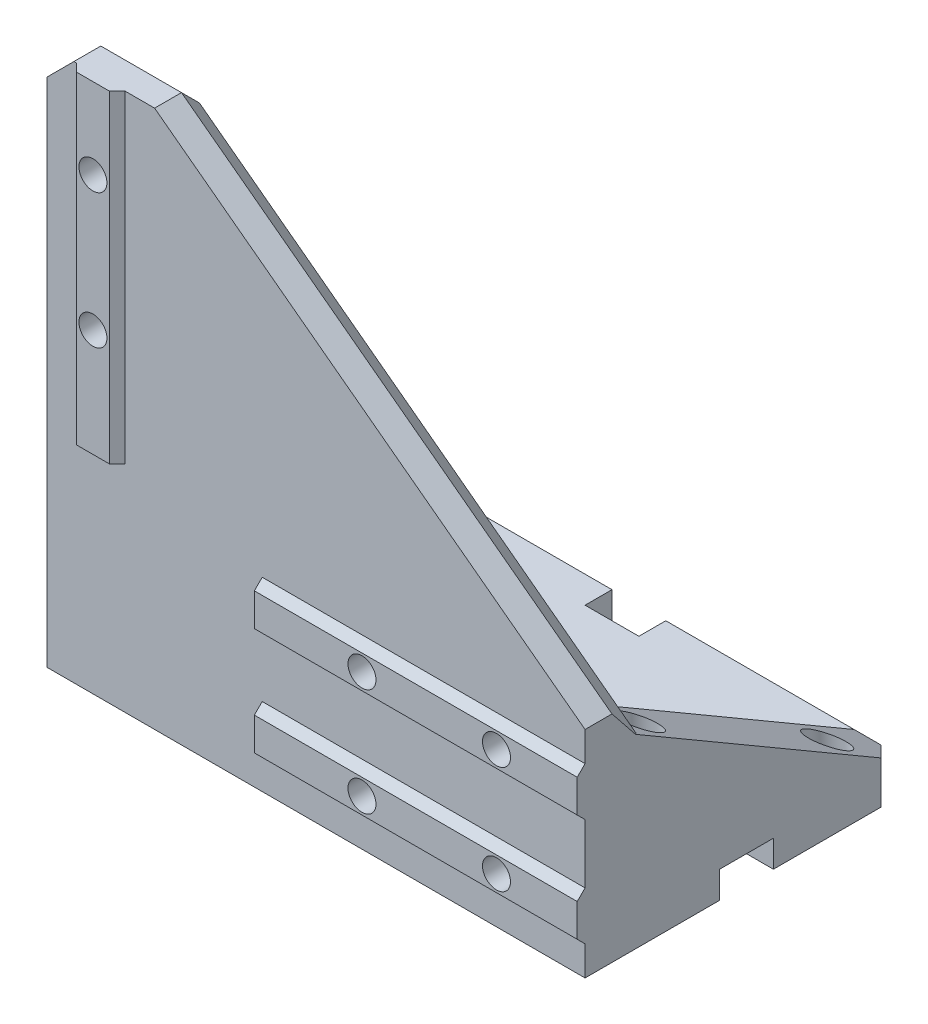
SolidWorks part; units mm, degrees
ref_plane "Płaszczyzna przednia" through (0, 0, 0) normal (0, 0, 1) x (1, 0, 0)
ref_plane "Płaszczyzna górna" through (0, 0, 0) normal (0, 1, 0) x (1, 0, 0)
ref_plane "Płaszczyzna prawa" through (0, 0, 0) normal (1, 0, 0) x (0, 0, -1)
sketch "Sketch1" plane through (0, 0, 0) normal (0, 0, 1) x (1, 0, 0)
  line L0 (0, 0) -> (100, 0)
  line L1 (100, 0) -> (100, 40)
  line L2 (100, 40) -> (20, 100)
  line L3 (20, 100) -> (0, 100)
  line L4 (0, 100) -> (0, 0)
  line L5 (10, 100) -> (10, 0) construction
  line L6 (30, 100) -> (30, 0) construction
  line L8 (100, 30) -> (0, 30) construction
  dimension "D1" = 20
  dimension "D2" = 40
  dimension "D3" = 100
extrude "Boss-Extrude1" add sketch "Sketch1" along normal blind 10
sketch "Sketch2" plane through (0, 0, 0) normal (0, 0, 1) x (1, 0, 0)
  line L5 (10, 100) -> (10, 0) construction
  line L7 (100, 10) -> (0, 10) construction
  line L8 (100, 30) -> (0, 30) construction
  line L9 (0, 0) -> (100, 0) construction
  line L10 (0, 100) -> (0, 0) construction
  line L11 (100, 0) -> (100, 40) construction
  line L12 (0, 100) -> (0, 0) construction
  line L13 (20, 100) -> (0, 100) construction
  line L14 (0, 0) -> (100, 0) construction
  circle A0 centre (10, 85) radius 2.6
  circle A2 centre (10, 60) radius 2.6
  circle A4 centre (85, 30) radius 2.6
  circle A5 centre (85, 10) radius 2.6
  circle A6 centre (60, 10) radius 2.6
  circle A7 centre (60, 30) radius 2.6
  dimension "D9" = 60
  dimension "D1" = 10
  dimension "D2" = 10
  dimension "D4" = 15
  dimension "D6" = 60
  dimension "D7" = 15
  dimension "D8" = 20
extrude "Cut-Extrude1" cut sketch "Sketch2" along normal through all
sketch "Sketch3" plane through (0, 0, 0) normal (0, 0, 1) x (1, 0, 0)
  line L0 (0, 100) -> (0, 0) construction
  line L1 (100, 0) -> (100, 40) construction
  line L2 (100, 25.5) -> (40, 25.5)
  line L3 (100, 25.5) -> (100, 34.5)
  line L4 (100, 34.5) -> (40, 34.5)
  line L5 (40, 25.5) -> (40, 34.5)
  line L6 (20, 100) -> (0, 100) construction
  line L7 (100, 5.5) -> (40, 5.5)
  line L8 (100, 5.5) -> (100, 14.5)
  line L9 (100, 14.5) -> (40, 14.5)
  line L10 (40, 5.5) -> (40, 14.5)
  line L11 (14.5, 100) -> (5.5, 100)
  line L12 (14.5, 100) -> (14.5, 40)
  line L13 (14.5, 40) -> (5.5, 40)
  line L14 (5.5, 100) -> (5.5, 40)
  line L15 (0, 0) -> (100, 0) construction
  circle A0 centre (60, 30) radius 2.6 construction
  circle A1 centre (60, 10) radius 2.6 construction
  circle A3 centre (10, 60) radius 2.6 construction
  dimension "D3" = 4.5
  dimension "D6" = 4.5
  dimension "D10" = 4.5
  dimension "D1" = 40
  dimension "D2" = 40
  dimension "D4" = 9
  dimension "D5" = 9
  dimension "D8" = 9
  dimension "D11" = 40
extrude "Boss-Extrude3" add sketch "Sketch3" along normal blind 1.46 from surface starting at face at (12.6, 85, 10)
extrude "Cut-Extrude2" cut sketch "Sketch2<2>" along normal through all both and the other way through all
sketch "Sketch2<2>" plane through (0, 0, 0) normal (0, 0, 1) x (1, 0, 0) same geometry as "Sketch2"
chamfer "Chamfer1" distance 1.46 angle 45 6 edges at (14.5, 70, 11.46) (5.5, 70, 11.46) (70, 5.5, 11.46) (70, 14.5, 11.46) (70, 25.5, 11.46) (70, 34.5, 11.46)
sketch "Sketch4" plane through (0, 0, 0) normal (0, 0, 1) x (1, 0, 0)
  circle A0 centre (10, 85) radius 4.5
  circle A3 centre (10, 60) radius 4.5
  circle A4 centre (60, 30) radius 4.5
  circle A5 centre (85, 30) radius 4.5
  circle A6 centre (85, 10) radius 4.5
  circle A7 centre (60, 10) radius 4.5
  dimension "D1" = 9
extrude "Cut-Extrude3" cut sketch "Sketch4" along normal blind 5 from surface starting at face at (12.6, 85, 0)
sketch "Sketch5" plane through (0, 0, 0) normal (0, 1, 0) x (1, 0, 0)
  line L0 (100, 25) -> (0, 25) construction
  line L1 (100, 50) -> (0, 50)
  line L2 (100, 50) -> (100, 0)
  line L4 (0, 50) -> (0, 0)
  line L5 (0, 0) -> (100, 0)
  line L7 (100, -10) -> (100, 0) construction
  line L12 (0, -10) -> (0, 0) construction
  dimension "D1" = 50
extrude "Boss-Extrude4" add sketch "Sketch5" along normal blind 5
sketch "Sketch8" plane through (0, 0, 0) normal (1, 0, 0) x (0, 0, -1)
  line L0 (-10, 5) -> (50, 5)
  line L1 (50, 5) -> (-10, 40)
  line L2 (-10, 40) -> (-10, 5)
  line L3 (-10, 34.5) -> (-10, 40) construction
  line L4 (-10, 100) -> (-10, 0) construction
extrude "Boss-Extrude5" add sketch "Sketch8" along normal blind 10
extrude "Boss-Extrude6" add sketch "Sketch8<2>" against normal blind 10 from surface starting at face at (100, 17.8571, 0.4171)
sketch "Sketch8<2>" plane through (0, 0, 0) normal (1, 0, 0) x (0, 0, -1) same geometry as "Sketch8"
sketch "Sketch10" plane through (0, 0, 0) normal (0, 1, 0) x (1, 0, 0)
  line L0 (0, -10) -> (0, 50) construction
  line L1 (95, 40) -> (5, 40) construction
  line L2 (95, 40) -> (95, 5) construction
  line L3 (95, 5) -> (5, 5) construction
  line L4 (5, 40) -> (5, 5) construction
  line L5 (95, 40) -> (5, 5) construction
  line L6 (95, 5) -> (5, 40) construction
  line L7 (100, -10) -> (100, 50) construction
  line L8 (100, 50) -> (0, 50) construction
  line L13 (0, -10) -> (100, -10) construction
  circle A0 centre (5, 40) radius 1.75
  circle A1 centre (95, 40) radius 1.75
  circle A2 centre (95, 5) radius 1.75
  circle A3 centre (5, 5) radius 1.75
  point P0 (50, 22.5)
  dimension "D5" = 3.5
  dimension "D1" = 5
  dimension "D2" = 5
  dimension "D3" = 10
  dimension "D4" = 15
extrude "Cut-Extrude4" cut sketch "Sketch10" along normal through all both and the other way through all
sketch "Sketch11" plane through (0, 0, 0) normal (0, 1, 0) x (1, 0, 0)
  circle A0 centre (5, 5) radius 3.5
  circle A1 centre (5, 40) radius 3.5
  circle A2 centre (95, 40) radius 3.5
  circle A3 centre (95, 5) radius 3.5
  dimension "D1" = 7
extrude "Cut-Extrude5" cut sketch "Sketch11" against normal up to surface (-5 mm away) from surface up to face at (50, 5, -25) starting at face at (10, 100, 7.865)
sketch "Sketch12" plane through (0, 0, 0) normal (0, 1, 0) x (1, 0, 0)
  line L5 (100, -10) -> (100, 50) construction
  line L6 (100, 25) -> (100, 15)
  line L7 (100, 25) -> (95, 25)
  line L8 (100, 15) -> (95, 15)
  line L9 (95, 25) -> (95, 15)
  line L10 (100, 50) -> (0, 50) construction
  line L11 (0, 15) -> (0, 25)
  line L12 (0, 15) -> (5, 15)
  line L13 (0, 25) -> (5, 25)
  line L14 (5, 15) -> (5, 25)
  line L15 (0, -10) -> (0, 50) construction
  line L16 (55, 50) -> (45, 50)
  line L17 (55, 50) -> (55, 45)
  line L18 (45, 50) -> (45, 45)
  line L19 (55, 45) -> (45, 45)
  dimension "D1" = 10
  dimension "D2" = 5
  dimension "D3" = 45
  dimension "D4" = 5
  dimension "D5" = 10
  dimension "D6" = 25
  dimension "D7" = 10
  dimension "D8" = 5
  dimension "D9" = 25
extrude "Cut-Extrude6" cut sketch "Sketch12" along normal blind 5
chamfer "Chamfer2" distance 5 angle 45 6 edges at (100, 2.5, -50) (0, 2.5, -50) (0, 100, 5) (60, 70, 0) (10, 100, 0) (0, 67.0833, 0)
